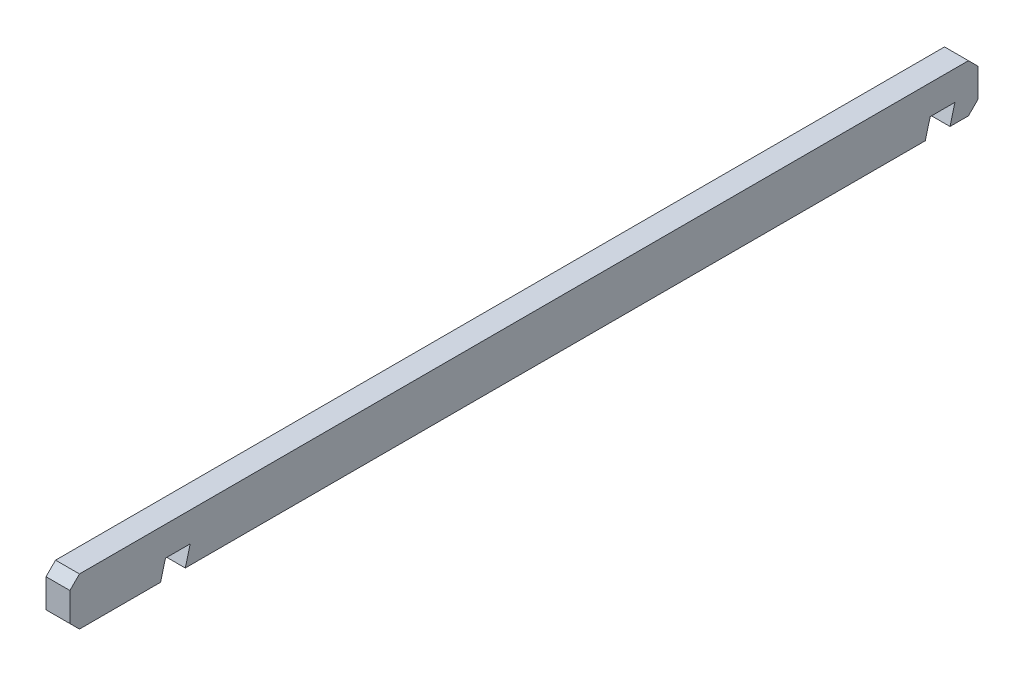
SolidWorks part; units mm, degrees
ref_plane "Front" through (0, 0, 0) normal (0, 0, 1) x (1, 0, 0)
ref_plane "Top" through (0, 0, 0) normal (0, 1, 0) x (1, 0, 0)
ref_plane "Right" through (0, 0, 0) normal (1, 0, 0) x (0, 0, -1)
sketch "Esquisse1" plane through (0, 0, 0) normal (0, 0, 1) x (1, 0, 0)
  line L1 (0, 0) -> (50, 0)
  line L2 (0, 0) -> (0, 100)
  line L3 (0, 100) -> (50, 100)
  line L4 (50, 0) -> (50, 100)
  dimension "D1" = 50
  dimension "D2" = 100
extrude "Boss.-Extru.1" add sketch "Esquisse1" along normal blind 1900
sketch "Esquisse2" plane through (0, 0, 0) normal (-1, 0, 0) x (0, 0, 1)
  line L0 (1710.3528, 0) -> (1700, 38.637)
  line L1 (1900, 0) -> (0, 0) construction
  line L2 (1700, 38.637) -> (1648.2362, 38.637)
  line L3 (1648.2362, 38.637) -> (1658.589, 0)
  line L4 (1658.589, 0) -> (1710.3528, 0)
  line L6 (1900, 100) -> (1900, 0) construction
  line L7 (110.3528, 0) -> (100, 38.637)
  line L8 (100, 38.637) -> (48.2362, 38.637)
  line L9 (48.2362, 38.637) -> (58.589, 0)
  line L10 (58.589, 0) -> (110.3528, 0)
  point P9 (211.3693, 0)
  dimension "D1" = 75
  dimension "D2" = 40
  dimension "D3" = 50
  dimension "D4" = 200
  dimension "D6" = 1600
  dimension "D5" = 2
extrude "Enlèv. mat.-Extru.1" cut sketch "Esquisse2" against normal up to vertex (50 mm away) up to point (50, 0, 1900)
chamfer "Chanfrein1" distance 20 angle 45 4 edges at (25, 100, 1900) (25, 0, 1900) (25, 0, 0) (25, 100, 0)
